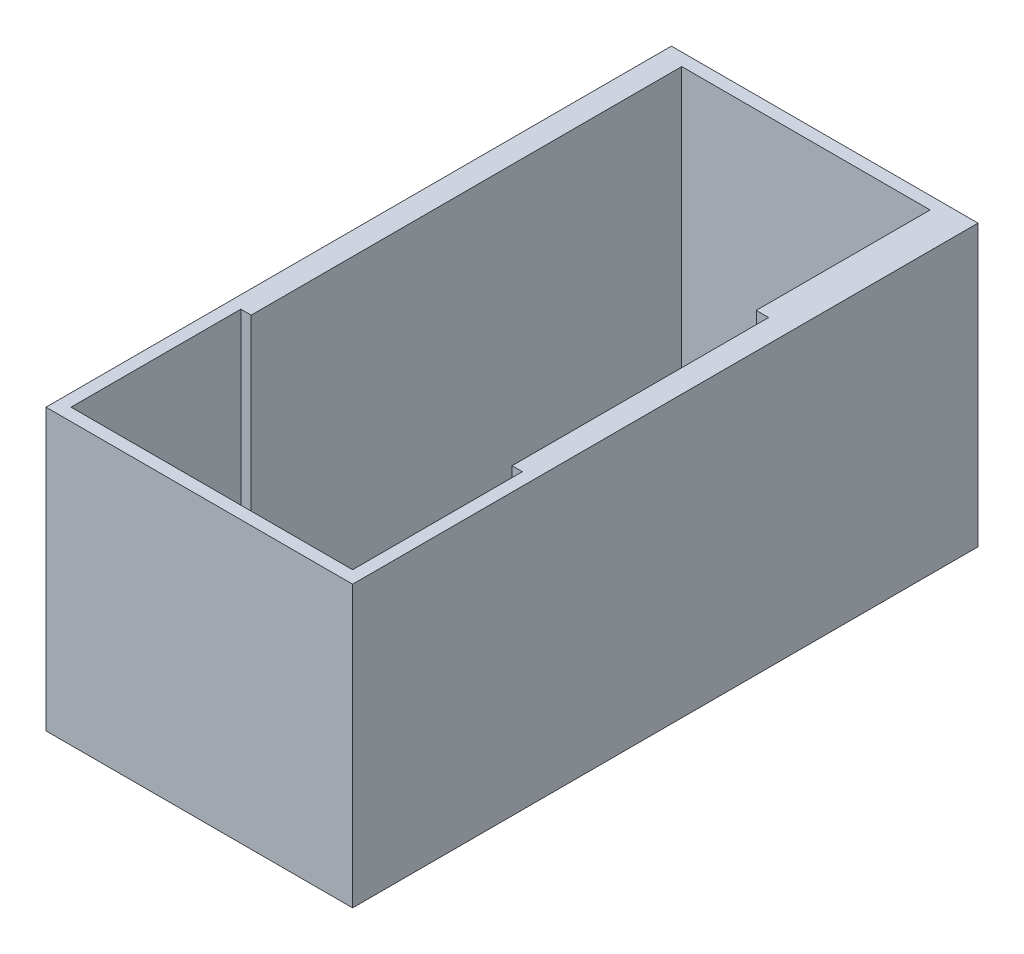
SolidWorks part; units mm, degrees
ref_plane "Front Plane" through (0, 0, 0) normal (0, 0, 1) x (1, 0, 0)
ref_plane "Top Plane" through (0, 0, 0) normal (0, 1, 0) x (1, 0, 0)
ref_plane "Right Plane" through (0, 0, 0) normal (1, 0, 0) x (0, 0, -1)
sketch "Sketch1" plane through (0, 0, 0) normal (0, 1, 0) x (1, 0, 0)
  line L0 (0, 0) -> (0, 2095.5) construction
  line L1 (-863.6, -520.7) -> (863.6, -520.7)
  line L2 (-863.6, -520.7) -> (-863.6, 520.7)
  line L3 (-863.6, 520.7) -> (863.6, 520.7)
  line L4 (863.6, -520.7) -> (863.6, 520.7)
  line L5 (-863.6, -520.7) -> (863.6, 520.7) construction
  line L6 (-863.6, 520.7) -> (863.6, -520.7) construction
  line L7 (-660.4, 520.7) -> (660.4, 520.7)
  line L8 (-660.4, 520.7) -> (-660.4, 1409.7)
  line L9 (-660.4, 1409.7) -> (660.4, 1409.7)
  line L10 (660.4, 520.7) -> (660.4, 1409.7)
  line L12 (-800.1, 1409.7) -> (800.1, 1409.7)
  line L13 (-800.1, 1409.7) -> (-800.1, 2095.5)
  line L14 (-800.1, 2095.5) -> (800.1, 2095.5)
  line L15 (800.1, 1409.7) -> (800.1, 2095.5)
  line L16 (-800.1, 2095.5) -> (723.9, 2095.5)
  line L17 (-800.1, 2095.5) -> (-800.1, 3162.3)
  line L18 (-800.1, 3162.3) -> (723.9, 3162.3)
  line L19 (723.9, 2095.5) -> (723.9, 3162.3)
  point P0 (0, 0)
  point P10 (0, 1409.7)
  point P13 (0, 2095.5)
  dimension "D1" = 1727.2
  dimension "D2" = 1041.4
  dimension "D3" = 1320.8
  dimension "D4" = 889
  dimension "D5" = 1600.2
  dimension "D6" = 685.8
  dimension "D7" = 1524
  dimension "D8" = 1066.8
sketch "Sketch2" plane through (0, 0, 0) normal (0, 1, 0) x (1, 0, 0)
  line L0 (-275, 3062.3) -> (-275, 3012.3) construction
  line L1 (-450, 3012.3) -> (-100, 3012.3)
  line L2 (-450, 3012.3) -> (-450, 2512.3)
  line L3 (-450, 2512.3) -> (-100, 2512.3)
  line L4 (-100, 3012.3) -> (-100, 2512.3)
  line L5 (-500, 3062.3) -> (-50, 3062.3)
  line L6 (-500, 3062.3) -> (-500, 2462.3)
  line L7 (-500, 2462.3) -> (-50, 2462.3)
  line L8 (-50, 3062.3) -> (-50, 2462.3)
  line L9 (-450, 2762.3) -> (-500, 2762.3) construction
  line L10 (100, 3012.3) -> (100, 2512.3)
  line L11 (100, 3012.3) -> (450, 3012.3)
  line L12 (450, 3012.3) -> (450, 2512.3)
  line L13 (100, 2512.3) -> (450, 2512.3)
  line L14 (50, 3062.3) -> (50, 2462.3)
  line L15 (50, 3062.3) -> (500, 3062.3)
  line L16 (500, 3062.3) -> (500, 2462.3)
  line L17 (50, 2462.3) -> (500, 2462.3)
  line L18 (100, 2312.3) -> (100, 1812.3)
  line L19 (100, 2312.3) -> (450, 2312.3)
  line L20 (450, 2312.3) -> (450, 1812.3)
  line L21 (100, 1812.3) -> (450, 1812.3)
  line L22 (50, 2362.3) -> (50, 1762.3)
  line L23 (50, 2362.3) -> (500, 2362.3)
  line L24 (500, 2362.3) -> (500, 1762.3)
  line L25 (50, 1762.3) -> (500, 1762.3)
  line L26 (100, 1612.3) -> (100, 1112.3)
  line L27 (100, 1612.3) -> (450, 1612.3)
  line L28 (450, 1612.3) -> (450, 1112.3)
  line L29 (100, 1112.3) -> (450, 1112.3)
  line L30 (50, 1662.3) -> (50, 1062.3)
  line L31 (50, 1662.3) -> (500, 1662.3)
  line L32 (500, 1662.3) -> (500, 1062.3)
  line L33 (50, 1062.3) -> (500, 1062.3)
  line L34 (100, 912.3) -> (100, 412.3)
  line L35 (100, 912.3) -> (450, 912.3)
  line L36 (450, 912.3) -> (450, 412.3)
  line L37 (100, 412.3) -> (450, 412.3)
  line L38 (50, 962.3) -> (50, 362.3)
  line L39 (50, 962.3) -> (500, 962.3)
  line L40 (500, 962.3) -> (500, 362.3)
  line L41 (50, 362.3) -> (500, 362.3)
  line L42 (-450, 2312.3) -> (-450, 1812.3)
  line L43 (-450, 2312.3) -> (-100, 2312.3)
  line L44 (-100, 2312.3) -> (-100, 1812.3)
  line L45 (-450, 1812.3) -> (-100, 1812.3)
  line L46 (-500, 2362.3) -> (-500, 1762.3)
  line L47 (-500, 2362.3) -> (-50, 2362.3)
  line L48 (-50, 2362.3) -> (-50, 1762.3)
  line L49 (-500, 1762.3) -> (-50, 1762.3)
  line L50 (-450, 1612.3) -> (-450, 1112.3)
  line L51 (-450, 1612.3) -> (-100, 1612.3)
  line L52 (-100, 1612.3) -> (-100, 1112.3)
  line L53 (-450, 1112.3) -> (-100, 1112.3)
  line L54 (-500, 1662.3) -> (-500, 1062.3)
  line L55 (-500, 1662.3) -> (-50, 1662.3)
  line L56 (-50, 1662.3) -> (-50, 1062.3)
  line L57 (-500, 1062.3) -> (-50, 1062.3)
  line L58 (-450, 912.3) -> (-450, 412.3)
  line L59 (-450, 912.3) -> (-100, 912.3)
  line L60 (-100, 912.3) -> (-100, 412.3)
  line L61 (-450, 412.3) -> (-100, 412.3)
  line L62 (-500, 962.3) -> (-500, 362.3)
  line L63 (-500, 962.3) -> (-50, 962.3)
  line L64 (-50, 962.3) -> (-50, 362.3)
  line L65 (-500, 362.3) -> (-50, 362.3)
  line L66 (-450, 3012.3) -> (100, 3012.3) construction
  line L67 (-450, 3012.3) -> (-450, 2312.3) construction
  line L68 (-50, 3062.3) -> (50, 3062.3) construction
  line L69 (0, 3062.3) -> (0, 2095.5) construction
  line L70 (-500, 2462.3) -> (-500, 2362.3)
  line L71 (-550, 3112.3) -> (550, 3112.3)
  line L72 (-550, 3112.3) -> (-550, 312.3)
  line L73 (-550, 312.3) -> (550, 312.3)
  line L74 (550, 3112.3) -> (550, 312.3)
  line L75 (-800.1, 3162.3) -> (723.9, 3162.3) construction
  dimension "D1" = 350
  dimension "D2" = 500
  dimension "D3" = 450
  dimension "D4" = 600
  dimension "D5" = 2
  dimension "D7" = 90
  dimension "D8" = 550
  dimension "D9" = 50
  dimension "D10" = 50
  dimension "D11" = 50
  dimension "D12" = 50
  dimension "D13" = 100
  dimension "D14" = 50
  dimension "D6" = 4
sketch "Resized Everything" plane through (0, 0, 0) normal (0, 1, 0) x (1, 0, 0)
  line L85 (-790.321, 2977.388) -> (-697.865, 2977.388)
  line L86 (-697.865, 2977.388) -> (-697.865, 3039.618)
  line L87 (-790.321, 3039.618) -> (-697.865, 3039.618)
  line L88 (-790.321, 2977.388) -> (-790.321, 3039.618)
  line L89 (-804.545, 2904.49) -> (-683.641, 2904.49)
  line L90 (-683.641, 2904.49) -> (-683.641, 2977.388)
  line L91 (-804.545, 2977.388) -> (-683.641, 2977.388)
  line L92 (-804.545, 2904.49) -> (-804.545, 2977.388)
  line L93 (-800.1, 3039.618) -> (-800.1, 3087.624)
  line L94 (-800.1, 3039.618) -> (-688.086, 3039.618)
  line L95 (-688.086, 3039.618) -> (-688.086, 3087.624)
  line L96 (-800.1, 3087.624) -> (-688.086, 3087.624)
  line L97 (-800.1, 3087.624) -> (-693.42, 3087.624)
  line L98 (-693.42, 3087.624) -> (-693.42, 3162.3)
  line L99 (-800.1, 3162.3) -> (-693.42, 3162.3)
  line L100 (-800.1, 3087.624) -> (-800.1, 3162.3)
  line L101 (-779.093, 3113.3) -> (-779.093, 3106.3)
  line L102 (-779.093, 3113.3) -> (-747.593, 3113.3)
  line L103 (-747.593, 3155.3) -> (-747.593, 3113.3)
  line L104 (-779.093, 3155.3) -> (-747.593, 3155.3)
  line L105 (-779.093, 3155.3) -> (-779.093, 3113.3)
  line L106 (-775.593, 3151.8) -> (-751.093, 3151.8)
  line L107 (-751.093, 3151.8) -> (-751.093, 3116.8)
  line L108 (-775.593, 3116.8) -> (-751.093, 3116.8)
  line L109 (-775.593, 3151.8) -> (-775.593, 3116.8)
  line L110 (-740.593, 3106.3) -> (-740.593, 3064.3)
  line L111 (-740.593, 3064.3) -> (-709.093, 3064.3)
  line L112 (-709.093, 3106.3) -> (-709.093, 3064.3)
  line L113 (-740.593, 3106.3) -> (-709.093, 3106.3)
  line L114 (-737.093, 3102.8) -> (-737.093, 3067.8)
  line L115 (-737.093, 3067.8) -> (-712.593, 3067.8)
  line L116 (-712.593, 3102.8) -> (-712.593, 3067.8)
  line L117 (-737.093, 3102.8) -> (-712.593, 3102.8)
  line L118 (-740.593, 3155.3) -> (-740.593, 3113.3)
  line L119 (-740.593, 3113.3) -> (-709.093, 3113.3)
  line L120 (-709.093, 3155.3) -> (-709.093, 3113.3)
  line L121 (-740.593, 3155.3) -> (-709.093, 3155.3)
  line L122 (-737.093, 3151.8) -> (-737.093, 3116.8)
  line L123 (-737.093, 3151.8) -> (-712.593, 3151.8)
  line L124 (-712.593, 3151.8) -> (-712.593, 3116.8)
  line L125 (-737.093, 3116.8) -> (-712.593, 3116.8)
  line L126 (-740.593, 3008.3) -> (-740.593, 2966.3)
  line L127 (-740.593, 2966.3) -> (-709.093, 2966.3)
  line L128 (-709.093, 3008.3) -> (-709.093, 2966.3)
  line L129 (-740.593, 3008.3) -> (-709.093, 3008.3)
  line L130 (-737.093, 3004.8) -> (-737.093, 2969.8)
  line L131 (-737.093, 2969.8) -> (-712.593, 2969.8)
  line L132 (-712.593, 3004.8) -> (-712.593, 2969.8)
  line L133 (-737.093, 3004.8) -> (-712.593, 3004.8)
  line L134 (-740.593, 3057.3) -> (-740.593, 3015.3)
  line L135 (-740.593, 3015.3) -> (-709.093, 3015.3)
  line L136 (-709.093, 3057.3) -> (-709.093, 3015.3)
  line L137 (-740.593, 3057.3) -> (-709.093, 3057.3)
  line L138 (-737.093, 3053.8) -> (-737.093, 3018.8)
  line L139 (-737.093, 3053.8) -> (-712.593, 3053.8)
  line L140 (-712.593, 3053.8) -> (-712.593, 3018.8)
  line L141 (-737.093, 3018.8) -> (-712.593, 3018.8)
  line L142 (-779.093, 3057.3) -> (-779.093, 3015.3)
  line L143 (-779.093, 3015.3) -> (-747.593, 3015.3)
  line L144 (-747.593, 3057.3) -> (-747.593, 3015.3)
  line L145 (-779.093, 3057.3) -> (-747.593, 3057.3)
  line L146 (-775.593, 3053.8) -> (-775.593, 3018.8)
  line L147 (-775.593, 3018.8) -> (-751.093, 3018.8)
  line L148 (-751.093, 3053.8) -> (-751.093, 3018.8)
  line L149 (-775.593, 3053.8) -> (-751.093, 3053.8)
  line L150 (-779.093, 3106.3) -> (-779.093, 3064.3)
  line L151 (-779.093, 3064.3) -> (-747.593, 3064.3)
  line L152 (-747.593, 3106.3) -> (-747.593, 3064.3)
  line L153 (-779.093, 3106.3) -> (-747.593, 3106.3)
  line L154 (-775.593, 3102.8) -> (-775.593, 3067.8)
  line L155 (-775.593, 3102.8) -> (-751.093, 3102.8)
  line L156 (-751.093, 3102.8) -> (-751.093, 3067.8)
  line L157 (-775.593, 3067.8) -> (-751.093, 3067.8)
  line L158 (-782.593, 3158.8) -> (-705.593, 3158.8)
  line L159 (-705.593, 3158.8) -> (-705.593, 2962.8)
  line L160 (-782.593, 2962.8) -> (-705.593, 2962.8)
  line L161 (-782.593, 3158.8) -> (-782.593, 2962.8)
  line L162 (-779.093, 3008.3) -> (-779.093, 2966.3)
  line L163 (-779.093, 2966.3) -> (-747.593, 2966.3)
  line L164 (-747.593, 3008.3) -> (-747.593, 2966.3)
  line L165 (-779.093, 3008.3) -> (-747.593, 3008.3)
  line L166 (-775.593, 3004.8) -> (-775.593, 2969.8)
  line L167 (-775.593, 3004.8) -> (-751.093, 3004.8)
  line L168 (-751.093, 3004.8) -> (-751.093, 2969.8)
  line L169 (-775.593, 2969.8) -> (-751.093, 2969.8)
sketch "Sketch6" plane through (0, 0, 0) normal (0, 1, 0) x (1, 0, 0)
  line L0 (-800.1, 3162.3) -> (723.9, 3162.3) construction
  line L1 (-748.0935, 2917.905) -> (-748.0935, 3167.3) construction
  line L2 (-809.2275, 2917.905) -> (-686.9595, 2917.905)
  line L3 (-686.9595, 2917.905) -> (-686.9595, 3167.3)
  line L4 (-686.9595, 3167.3) -> (-809.2275, 3167.3)
  line L5 (-696.087, 3048.381) -> (-696.087, 2990.596)
  line L6 (-800.1, 3048.381) -> (-800.1, 2990.596)
  line L7 (-809.2275, 2917.905) -> (-809.2275, 3167.3)
  line L8 (-701.04, 3162.3) -> (-696.087, 3162.3)
  line L9 (-696.087, 3162.3) -> (-696.087, 3092.958)
  line L16 (-791.0195, 2990.596) -> (-705.1675, 2990.596)
  line L17 (-705.1675, 2990.596) -> (-705.1675, 3048.381)
  line L18 (-791.0195, 3048.381) -> (-705.1675, 3048.381)
  line L19 (-791.0195, 2990.596) -> (-791.0195, 3048.381)
  line L20 (-804.2275, 2922.905) -> (-691.9595, 2922.905)
  line L21 (-691.9595, 2922.905) -> (-691.9595, 2990.596)
  line L22 (-804.2275, 2990.596) -> (-691.9595, 2990.596)
  line L23 (-804.2275, 2922.905) -> (-804.2275, 2990.596)
  line L24 (-800.1, 3048.381) -> (-800.1, 3092.958)
  line L25 (-800.1, 3048.381) -> (-696.087, 3048.381)
  line L26 (-696.087, 3048.381) -> (-696.087, 3092.958)
  line L27 (-800.1, 3092.958) -> (-696.087, 3092.958)
  line L28 (-800.1, 3092.958) -> (-701.04, 3092.958)
  line L29 (-701.04, 3092.958) -> (-701.04, 3162.3)
  line L30 (-800.1, 3162.3) -> (-701.04, 3162.3)
  line L31 (-800.1, 3092.958) -> (-800.1, 3162.3)
  point P3 (-748.0935, 2922.905)
  dimension "D1" = 239.395
  dimension "D2" = 5
  dimension "D3" = 5
  dimension "D4" = 5
extrude "Boss-Extrude1" add sketch "Sketch6" along normal blind 111.8 contours L2 L1 L20 L23 L22 L6 L24 L31 L30 L4 L7 | L1 L2 L3 L4 L30 L29 L27 L26 L5 L22 L21 L20 | L29 L27 L9 L8 region at (-778.6605, 0, -2920.4728) region at (-745.5257, 0, -2920.405) region at (-698.5635, 0, -3127.629)
equation "\"alpha\"= 1"
equation "\"bin_width\"= 0.5"
equation "\"bin_depth\"= 0.35"
equation "\"bin_height\"= 0.35"
